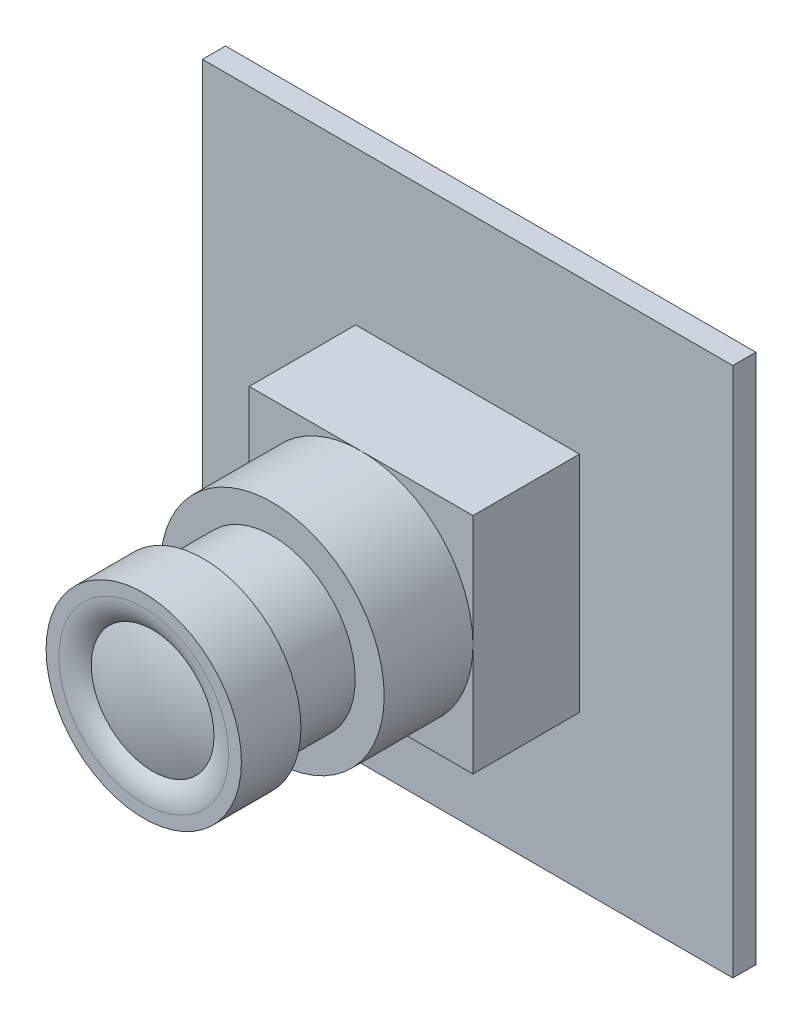
SolidWorks part; units mm, degrees
ref_plane "Front Plane" through (0, 0, 0) normal (0, 0, 1) x (1, 0, 0)
ref_plane "Top Plane" through (0, 0, 0) normal (0, 1, 0) x (1, 0, 0)
ref_plane "Right Plane" through (0, 0, 0) normal (1, 0, 0) x (0, 0, -1)
sketch "Sketch1" plane through (0, 0, 0) normal (0, 0, 1) x (1, 0, 0)
  line L1 (0, 37.9349) -> (37.9349, 37.9349)
  line L2 (0, 37.9349) -> (0, 0)
  line L3 (0, 0) -> (37.9349, 0)
  line L4 (37.9349, 37.9349) -> (37.9349, 0)
  dimension "D1" = 37.9349
extrude "Boss-Extrude1" add sketch "Sketch1" along normal blind 1.651
sketch "Sketch2" plane through (0, 0, 1.651) normal (0, 0, 1) x (1, 0, 0)
  line L0 (37.9349, 18.9675) -> (26.9685, 18.9675) construction
  line L1 (10.9665, 26.9685) -> (26.9684, 26.9685)
  line L2 (10.9665, 26.9685) -> (10.9665, 10.9665)
  line L3 (10.9665, 10.9665) -> (26.9685, 10.9665)
  line L4 (26.9684, 26.9685) -> (26.9685, 10.9665)
  line L5 (0, 0) -> (37.9349, 0) construction
  line L6 (37.9349, 0) -> (37.9349, 37.9349) construction
  line L7 (18.9674, 37.9349) -> (18.9675, 26.9685) construction
  line L10 (37.9349, 37.9349) -> (0, 37.9349) construction
  dimension "D1" = 16.002
extrude "Boss-Extrude2" add sketch "Sketch2" along normal blind 7.62
sketch "Sketch3" plane through (0, 0, 9.271) normal (0, 0, 1) x (1, 0, 0)
  line L1 (26.9684, 26.9685) -> (10.9665, 26.9685) construction
  line L2 (26.9685, 10.9665) -> (26.9684, 26.9685) construction
  line L3 (10.9665, 26.9685) -> (10.9665, 10.9665) construction
  line L4 (10.9665, 10.9665) -> (26.9685, 10.9665) construction
  circle A0 centre (18.9675, 18.9675) radius 8.001
extrude "Boss-Extrude3" add sketch "Sketch3" along normal blind 6.35
sketch "Sketch4" plane through (0, 0, 15.621) normal (0, 0, 1) x (1, 0, 0)
  circle A0 centre (18.9675, 18.9675) radius 5.9309
  circle A1 centre (18.9675, 18.9675) radius 8.001 construction
  dimension "D1" = 11.8618
extrude "Boss-Extrude4" add sketch "Sketch4" along normal blind 4.9403
sketch "Sketch5" plane through (0, 0, 20.5613) normal (0, 0, 1) x (1, 0, 0)
  circle A0 centre (18.9675, 18.9675) radius 6.985
  circle A1 centre (18.9675, 18.9675) radius 5.9309 construction
  dimension "D1" = 13.97
extrude "Boss-Extrude5" add sketch "Sketch5" along normal blind 4.2545
sketch "Sketch6" plane through (0, 0, 24.8158) normal (0, 0, 1) x (1, 0, 0)
  circle A0 centre (18.9675, 18.9675) radius 4.3878
  circle A1 centre (18.9675, 18.9675) radius 6.985 construction
  dimension "D1" = 8.7757
extrude "Cut-Extrude1" cut sketch "Sketch6" against normal blind 0.635
fillet "Fillet2" radius 2.54 1 edges at (23.3553, 18.9675, 24.8158)
dome "Dome1" faces to dome 1 distance 0.762 reverse direction no elliptical dome no face at (23.3553, 18.9675, 24.1808) parameters "D1"=0.762
sketch "Sketch9" plane through (0, 0, 1.651) normal (0, 0, 1) x (1, 0, 0)
  line L0 (32.8168, 32.8168) -> (37.9349, 32.8168) construction
  line L1 (0, 0) -> (37.9349, 0) construction
  line L2 (37.9349, 0) -> (37.9349, 37.9349) construction
  line L3 (32.8168, 37.9349) -> (32.8168, 32.8168) construction
  line L4 (0, 37.9349) -> (0, 0) construction
  line L5 (37.9349, 37.9349) -> (0, 37.9349) construction
  line L6 (5.1181, 37.9349) -> (5.1181, 32.8168) construction
  line L7 (0, 32.8168) -> (5.1181, 32.8168) construction
  line L8 (5.1181, 0) -> (5.1181, 5.1181) construction
  line L9 (0, 5.1181) -> (5.1181, 5.1181) construction
  line L10 (37.9349, 5.1181) -> (32.8168, 5.1181) construction
  line L11 (32.8168, 0) -> (32.8168, 5.1181) construction
  line L12 (18.9674, 37.9349) -> (18.9674, 36.1569) construction
  line L13 (15.508, 36.1569) -> (22.4269, 36.1569)
  line L14 (22.4269, 35.0692) -> (23.5146, 35.0692) construction
  line L15 (15.508, 33.9815) -> (22.4269, 33.9815)
  line L16 (15.508, 35.0692) -> (22.4269, 35.0692) construction
  line L17 (18.9674, 33.9815) -> (18.9675, 26.9685) construction
  line L18 (26.9684, 26.9685) -> (10.9665, 26.9685) construction
  line L19 (14.4203, 35.0692) -> (15.508, 35.0692) construction
  line L20 (15.375, 3.9534) -> (22.5599, 3.9534)
  line L21 (22.4269, 2.8739) -> (23.5146, 2.8739) construction
  line L22 (15.375, 1.7943) -> (22.5599, 1.7943)
  line L23 (15.508, 2.8739) -> (22.4269, 2.8739) construction
  line L24 (14.4203, 2.8739) -> (15.508, 2.8739) construction
  line L25 (33.9815, 22.5599) -> (33.9815, 15.375)
  line L26 (18.9675, 10.9665) -> (18.9675, 3.9534) construction
  line L27 (18.9675, 3.9534) -> (18.9674, 1.7943) construction
  line L28 (36.1394, 22.5599) -> (36.1394, 15.375)
  line L29 (10.9665, 10.9665) -> (26.9685, 10.9665) construction
  line L30 (18.9674, 1.7943) -> (18.9674, 0) construction
  line L31 (18.9674, 36.1569) -> (18.9674, 33.9815) construction
  line L32 (33.9815, 15.375) -> (36.1394, 15.375) construction
  line L33 (35.0604, 22.4269) -> (35.0604, 15.508) construction
  line L34 (35.0604, 23.5141) -> (35.0604, 22.4269) construction
  line L35 (35.0604, 15.508) -> (35.0604, 14.4209) construction
  line L36 (26.9685, 18.9675) -> (33.9815, 18.9675) construction
  line L37 (26.9685, 10.9665) -> (26.9684, 26.9685) construction
  line L38 (1.7955, 22.5599) -> (1.7955, 15.375)
  line L39 (3.9534, 22.5599) -> (3.9534, 15.375)
  line L40 (1.7955, 15.375) -> (3.9534, 15.375) construction
  line L41 (2.8745, 22.4269) -> (2.8745, 15.508) construction
  line L42 (2.8745, 23.5141) -> (2.8745, 22.4269) construction
  line L43 (2.8745, 15.508) -> (2.8745, 14.4209) construction
  line L44 (3.9534, 18.9675) -> (10.9665, 18.9675) construction
  line L45 (10.9665, 26.9685) -> (10.9665, 10.9665) construction
  line L46 (1.7955, 22.5599) -> (3.9534, 22.5599) construction
  line L47 (0, 18.9675) -> (1.7955, 18.9675) construction
  line L48 (2.1209, 37.9349) -> (2.1209, 35.814) construction
  line L49 (0, 35.814) -> (2.1209, 35.814) construction
  line L50 (2.1209, 35.814) -> (10.9542, 35.814)
  line L51 (2.1209, 34.7091) -> (10.9542, 34.7091)
  line L52 (2.1209, 35.814) -> (2.1209, 34.7091) construction
  line L53 (10.4978, 35.2616) -> (11.2144, 35.2616) construction
  line L54 (2.1209, 35.814) -> (2.1209, 26.9807)
  line L55 (3.2258, 35.814) -> (3.2258, 26.9807)
  line L56 (2.6734, 27.4366) -> (2.6734, 26.7203) construction
  line L57 (0, 2.1209) -> (2.1209, 2.1209) construction
  line L58 (2.1209, 0) -> (2.1209, 2.1209) construction
  line L59 (2.1209, 2.1209) -> (2.1209, 12.0596)
  line L60 (3.2258, 2.1209) -> (3.2258, 12.0596)
  line L61 (2.1209, 2.1209) -> (3.2258, 2.1209) construction
  line L62 (2.6733, 11.6032) -> (2.6734, 12.3198) construction
  line L63 (2.1209, 2.1209) -> (12.0596, 2.1209)
  line L64 (2.1209, 3.2258) -> (12.0596, 3.2258)
  line L65 (11.6037, 2.6734) -> (12.32, 2.6734) construction
  line L66 (35.814, 0) -> (35.814, 2.1209) construction
  line L67 (37.9349, 2.1209) -> (35.814, 2.1209) construction
  line L68 (35.814, 2.1209) -> (25.8753, 2.1209)
  line L69 (35.814, 3.2258) -> (25.8753, 3.2258)
  line L70 (35.814, 2.1209) -> (35.814, 3.2258) construction
  line L71 (26.3317, 2.6733) -> (25.6151, 2.6734) construction
  line L72 (35.814, 2.1209) -> (35.814, 12.0596)
  line L73 (34.7091, 2.1209) -> (34.7091, 12.0596)
  line L74 (35.2615, 11.6037) -> (35.2615, 12.32) construction
  line L75 (35.814, 7.0903) -> (37.9349, 7.0903) construction
  line L76 (25.8753, 3.2258) -> (25.8753, 2.1209) construction
  line L77 (37.9349, 35.814) -> (35.814, 35.814) construction
  line L78 (35.814, 37.9349) -> (35.814, 35.814) construction
  line L79 (35.814, 35.814) -> (35.814, 25.8753)
  line L80 (34.7091, 35.814) -> (34.7091, 25.8753)
  line L81 (35.814, 35.814) -> (34.7091, 35.814) construction
  line L82 (35.2616, 26.3317) -> (35.2616, 25.6151) construction
  line L83 (35.814, 35.814) -> (25.8753, 35.814)
  line L84 (35.814, 34.7091) -> (25.8753, 34.7091)
  line L85 (26.3312, 35.2615) -> (25.6149, 35.2615) construction
  line L86 (30.8446, 37.9349) -> (30.8446, 35.814) construction
  line L87 (34.7091, 25.8753) -> (35.814, 25.8753) construction
  circle A0 centre (32.8168, 32.8168) radius 1.1176
  circle A1 centre (5.1181, 32.8168) radius 1.1176
  circle A2 centre (5.1181, 5.1181) radius 1.1176
  circle A3 centre (32.8168, 5.1181) radius 1.1176
  arc A4 (22.4269, 36.1569) -> (22.4269, 33.9815) centre (22.4269, 35.0692) cw
  arc A5 (15.508, 36.1569) -> (15.508, 33.9815) centre (15.508, 35.0692) ccw
  arc A6 (22.5599, 3.9534) -> (22.5599, 1.7943) centre (22.4269, 2.8739) cw
  arc A7 (15.375, 3.9534) -> (15.375, 1.7943) centre (15.508, 2.8739) ccw
  arc A8 (33.9815, 22.5599) -> (36.1394, 22.5599) centre (35.0604, 22.4269) cw
  arc A9 (33.9815, 15.375) -> (36.1394, 15.375) centre (35.0604, 15.508) ccw
  arc A10 (1.7955, 22.5599) -> (3.9534, 22.5599) centre (2.8745, 22.4269) cw
  arc A11 (1.7955, 15.375) -> (3.9534, 15.375) centre (2.8745, 15.508) ccw
  arc A12 (1.016, 35.814) -> (2.1209, 34.7091) centre (2.1204, 35.8135) ccw
  arc A13 (10.9542, 35.814) -> (10.9542, 34.7091) centre (10.4978, 35.2616) cw
  arc A14 (2.1209, 26.9807) -> (3.2258, 26.9807) centre (2.6734, 27.4366) ccw
  circle A15 centre (2.1209, 2.1209) radius 1.1049
  arc A16 (2.1209, 12.0596) -> (3.2258, 12.0596) centre (2.6733, 11.6032) cw
  arc A17 (12.0596, 2.1209) -> (12.0596, 3.2258) centre (11.6037, 2.6734) ccw
  circle A18 centre (35.814, 2.1209) radius 1.1049
  arc A19 (25.8753, 2.1209) -> (25.8753, 3.2258) centre (26.3317, 2.6733) cw
  arc A20 (35.814, 12.0596) -> (34.7091, 12.0596) centre (35.2615, 11.6037) ccw
  circle A21 centre (35.814, 35.814) radius 1.1049
  arc A22 (35.814, 25.8753) -> (34.7091, 25.8753) centre (35.2616, 26.3317) cw
  arc A23 (25.8753, 35.814) -> (25.8753, 34.7091) centre (26.3312, 35.2615) ccw
  arc A24 (3.2258, 35.814) -> (1.016, 35.814) centre (2.1209, 35.814) ccw
  dimension "D1" = 2.2352
  dimension "D3" = 1.0877
  dimension "D19" = 1.1054
  dimension "D24" = 2.2098
  dimension "D29" = 2.2098
  dimension "D35" = 2.2098
  dimension "D2" = 5.1181
  dimension "D4" = 1.778
  dimension "D5" = 7.013
  dimension "D6" = 6.919
  dimension "D7" = 1.0877
  dimension "D8" = 6.919
  dimension "D9" = 7.013
  dimension "D10" = 2.1591
  dimension "D11" = 1.7943
  dimension "D12" = 6.919
  dimension "D13" = 1.0871
  dimension "D14" = 7.013
  dimension "D15" = 6.919
  dimension "D16" = 1.0871
  dimension "D17" = 7.013
  dimension "D18" = 1.7955
  dimension "D20" = 2.1209
  dimension "D21" = 8.8333
  dimension "D22" = 0.7163
  dimension "D23" = 0.7166
  dimension "D25" = 9.9387
  dimension "D26" = 0.7166
  dimension "D27" = 0.7163
  dimension "D28" = 2.1209
  dimension "D30" = 9.9387
  dimension "D31" = 0.7166
  dimension "D32" = 0.7163
  dimension "D33" = 2.1209
  dimension "D34" = 2.1209
  dimension "D36" = 9.9387
  dimension "D37" = 0.7166
  dimension "D38" = 0.7163
  dimension "D39" = 2.1209
  dimension "D40" = 2.1209
